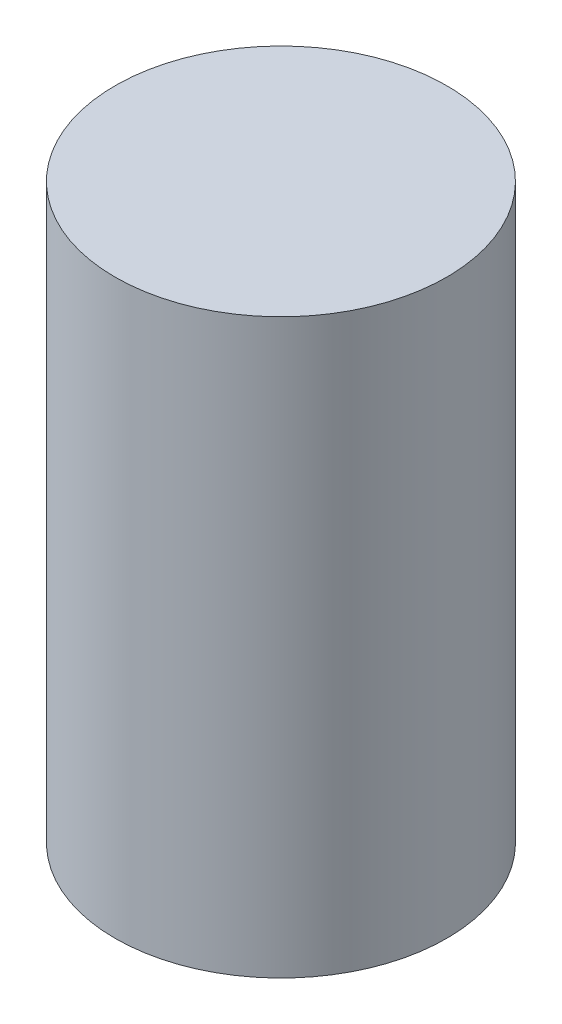
SolidWorks part; units mm, degrees
ref_plane "Front Plane" through (0, 0, 0) normal (0, 0, 1) x (1, 0, 0)
ref_plane "Top Plane" through (0, 0, 0) normal (0, 1, 0) x (1, 0, 0)
ref_plane "Right Plane" through (0, 0, 0) normal (1, 0, 0) x (0, 0, -1)
sketch "Sketch2" plane through (0, 0, 0) normal (0, 1, 0) x (1, 0, 0)
  circle A0 centre (0, 0) radius 6.95
  dimension "D1" = 13.9
extrude "Boss-Extrude1" add sketch "Sketch2" along normal blind 24
